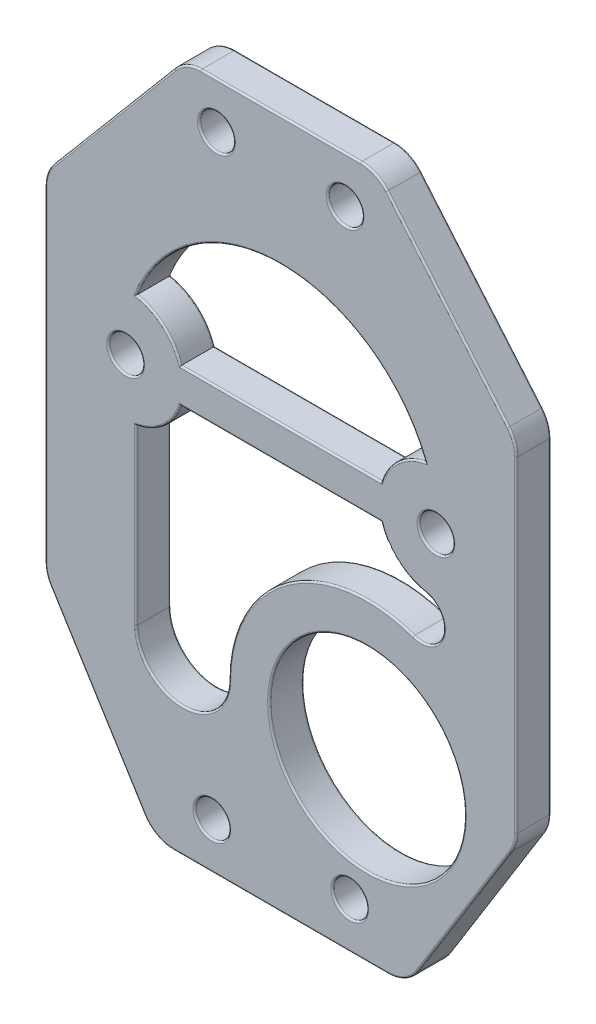
SolidWorks part; units mm, degrees
material "ABS"
ref_plane "Спереди" through (0, 0, 0) normal (0, 0, 1) x (1, 0, 0)
ref_plane "Сверху" through (0, 0, 0) normal (0, 1, 0) x (1, 0, 0)
ref_plane "Справа" through (0, 0, 0) normal (1, 0, 0) x (0, 0, -1)
sketch "Эскиз1" plane through (0, 0, 0) normal (0, 0, 1) x (1, 0, 0)
  line L0 (0, 0) -> (0, 60) construction
  line L1 (11, 0) -> (-11, 0)
  line L2 (-11, 0) -> (-20.5, 15.2889)
  line L3 (-20.5, 15.2889) -> (-20.5, 45.5889)
  line L4 (-20.5, 45.5889) -> (-8.3492, 60)
  line L5 (-8.3492, 60) -> (8.3492, 60)
  line L6 (20.5, 45.5889) -> (8.3492, 60)
  line L7 (20.5, 15.2889) -> (20.5, 45.5889)
  line L8 (11, 0) -> (20.5, 15.2889)
  line L9 (-13.5, 35.2889) -> (13.5, 35.2889) construction
  line L10 (-8.7303, 36.7889) -> (8.7303, 36.7889)
  line L11 (8.7303, 33.7889) -> (-8.7303, 33.7889) construction
  line L12 (8.7303, 33.7889) -> (8.7303, 36.7889) construction
  line L13 (8.7303, 36.7889) -> (-8.7303, 36.7889) construction
  line L14 (-8.7303, 33.7889) -> (-8.7303, 36.7889) construction
  line L15 (8.7303, 33.7889) -> (-8.7303, 36.7889) construction
  line L16 (8.7303, 36.7889) -> (-8.7303, 33.7889) construction
  line L17 (-8.7303, 33.7889) -> (8.7303, 33.7889)
  line L18 (13.5, 35.2889) -> (11.5456, 26.5864) construction
  line L19 (-12.5741, 30.3754) -> (-12.5741, 15.2889)
  circle A0 centre (-5.5992, 56) radius 1.5
  circle A1 centre (-13.5, 35.2889) radius 1.5
  circle A2 centre (-6, 4) radius 1.5
  circle A3 centre (6, 4) radius 1.5
  circle A4 centre (13.5, 35.2889) radius 1.5
  circle A5 centre (5.5992, 56) radius 1.5
  circle A6 centre (7.5, 15.2889) radius 8.5
  circle A7 centre (13.5, 35.2889) radius 5 construction
  circle A8 centre (-13.5, 35.2889) radius 5 construction
  circle A9 centre (7.5, 15.2889) radius 12 construction
  arc A10 (-12.5741, 40.2024) -> (12.5741, 40.2024) centre (0, 35.2889) cw
  arc A11 (-12.5741, 40.2024) -> (-8.7303, 36.7889) centre (-13.5, 35.2889) cw
  arc A12 (8.7303, 36.7889) -> (12.5741, 40.2024) centre (13.5, 35.2889) cw
  arc A13 (-8.7303, 33.7889) -> (-12.5741, 30.3754) centre (-13.5, 35.2889) cw
  arc A14 (8.7303, 33.7889) -> (12.5741, 30.3754) centre (13.5, 35.2889) ccw
  arc A15 (12.5741, 30.3754) -> (11.5456, 26.5864) centre (12.2094, 28.4403) cw
  arc A16 (11.5456, 26.5864) -> (-4.5, 15.2889) centre (7.5, 15.2889) ccw
  arc A17 (-12.5741, 15.2889) -> (-4.5, 15.2889) centre (-8.537, 15.2889) ccw
  dimension "D2" = 3
  dimension "D14" = 17
  dimension "D19" = 13.5
  dimension "D1" = 60
  dimension "D3" = 6
  dimension "D4" = 4
  dimension "D5" = 11
  dimension "D6" = 18
  dimension "D7" = 30.3
  dimension "D8" = 7
  dimension "D9" = 10.3
  dimension "D10" = 2.75
  dimension "D11" = 4
  dimension "D12" = 18.85
  dimension "D13" = 20.5
  dimension "D15" = 13
  dimension "D20" = 3
  dimension "D16" = 3.5
  dimension "D17" = 3.5
  dimension "D18" = 3.5
extrude "Бобышка-Вытянуть1" add sketch "Эскиз1" along normal blind 3
fillet "Скругление1" radius 3 8 edges at (-20.5, 45.5889, 1.5) (-8.3492, 60, 1.5) (8.3492, 60, 1.5) (20.5, 45.5889, 1.5) (20.5, 15.2889, 1.5) (11, 0, 1.5) (-11, 0, 1.5) (-20.5, 15.2889, 1.5)
fillet "Скругление2" radius 0.15 68 edges at (0.5916, 25.1008, 0) (-8.537, 11.2518, 0) (-12.5741, 22.8321, 0) (-10.1799, 31.5503, 0) (0, 33.7889, 0) (10.1799, 31.5503, 0) (14.1098, 27.9244, 0) (4.0992, 56, 0) (4.5, 4, 0) (-4.5, 4, 0) (-4.0992, 56, 0) (-20.3848, 15.3218, 0) (-15.9642, 7.9892, 0) (-10.7899, 0.378, 0) (0, 0, 0) (10.7899, 0.378, 0) (15.9642, 7.9892, 0) (20.3848, 15.3218, 0) (20.5, 30.319, 0) (20.3179, 45.5223, 0) (14.5208, 52.6803, 0) (8.2192, 59.7204, 0) (0, 60, 0) (-8.2192, 59.7204, 0) (-14.5208, 52.6803, 0) (-20.3179, 45.5223, 0) (-20.5, 30.319, 0) (-12, 35.2889, 0) (16, 15.2889, 0) (10.1799, 39.0275, 0) (0, 36.7889, 0) (-10.1799, 39.0275, 0) (0, 48.7889, 0) (12, 35.2889, 0) (0, 33.7889, 3) (-10.1799, 31.5503, 3) (-12.5741, 22.8321, 3) (-8.537, 11.2518, 3) (0.5916, 25.1008, 3) (14.1098, 27.9244, 3) (10.1799, 31.5503, 3) (16, 15.2889, 3) (-4.5, 4, 3) (-12, 35.2889, 3) (-4.0992, 56, 3) (-8.2192, 59.7204, 3) (0, 60, 3) (8.2192, 59.7204, 3) (14.5208, 52.6803, 3) (20.3179, 45.5223, 3) (20.5, 30.319, 3) (20.3848, 15.3218, 3) (15.9642, 7.9892, 3) (10.7899, 0.378, 3) (0, 0, 3) (-10.7899, 0.378, 3) (-15.9642, 7.9892, 3) (-20.3848, 15.3218, 3) (-20.5, 30.319, 3) (-20.3179, 45.5223, 3) (-14.5208, 52.6803, 3) (0, 36.7889, 3) (10.1799, 39.0275, 3) (0, 48.7889, 3) (-10.1799, 39.0275, 3) (4.5, 4, 3) (12, 35.2889, 3) (4.0992, 56, 3)
scale "Масштаб1" scale about centroid uniform scaling yes scale factor 2.2
equation "\"Scale\"= 1"
